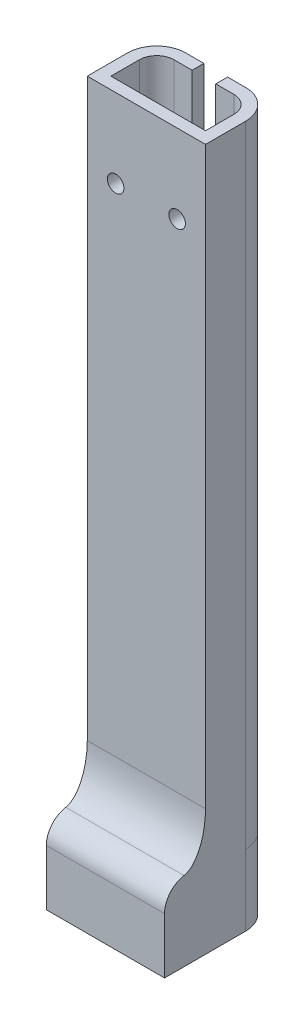
SolidWorks part; units mm, degrees
ref_plane "Front Plane" through (0, 0, 0) normal (0, 0, 1) x (1, 0, 0)
ref_plane "Top Plane" through (0, 0, 0) normal (0, 1, 0) x (1, 0, 0)
ref_plane "Right Plane" through (0, 0, 0) normal (1, 0, 0) x (0, 0, -1)
sketch "Sketch1" plane through (0, 0, 0) normal (0, 1, 0) x (1, 0, 0)
  line L1 (-7.5, 4.4) -> (7.5, 4.4)
  line L2 (-7.5, 4.4) -> (-7.5, -4.4)
  line L3 (-7.5, -4.4) -> (7.5, -4.4)
  line L4 (7.5, 4.4) -> (7.5, -4.4)
  line L5 (-7.5, 4.4) -> (7.5, -4.4) construction
  line L6 (-7.5, -4.4) -> (7.5, 4.4) construction
  point P0 (0, 0)
  dimension "D1" = 15
  dimension "D2" = 8.8
extrude "Boss-Extrude1" add sketch "Sketch1" along normal blind 80
fillet "Fillet1" radius 3.7 2 edges at (7.5, 40, -4.4) (-7.5, 40, -4.4)
sketch "Sketch3" plane through (0, 80, 0) normal (0, 1, 0) x (1, 0, 0)
  line L8 (-6, 0.7) -> (-6, -2.9)
  line L9 (-6, -2.9) -> (6, -2.9)
  line L10 (6, -2.9) -> (6, 0.7)
  line L11 (3.8, 2.9) -> (-3.8, 2.9)
  line L12 (-6, 0.7) -> (-6, -2.9)
  line L13 (-6, -2.9) -> (6, -2.9)
  line L14 (6, -2.9) -> (6, 0.7)
  line L15 (3.8, 2.9) -> (-3.8, 2.9)
  arc A4 (6, 0.7) -> (3.8, 2.9) centre (3.8, 0.7) ccw
  arc A5 (-3.8, 2.9) -> (-6, 0.7) centre (-3.8, 0.7) ccw
  arc A6 (6, 0.7) -> (3.8, 2.9) centre (3.8, 0.7) ccw
  arc A7 (-3.8, 2.9) -> (-6, 0.7) centre (-3.8, 0.7) ccw
  dimension "D1" = 1.5
extrude "Cut-Extrude1" cut sketch "Sketch3" against normal blind 26
sketch "Sketch4" plane through (0, 0, 4.4) normal (0, 0, 1) x (1, 0, 0)
  line L0 (-7.5, 80) -> (7.5, 80) construction
  line L1 (-7.5, 80) -> (-7.5, 0) construction
  line L2 (7.5, 80) -> (7.5, 0) construction
  circle A0 centre (-3.9, 70) radius 1.05
  circle A1 centre (3.9, 70) radius 1.05
  dimension "D3" = 2.1
  dimension "D4" = 2.1
  dimension "D1" = 10
  dimension "D2" = 10
  dimension "D5" = 3.6
  dimension "D6" = 3.6
extrude "Cut-Extrude2" cut sketch "Sketch4" against normal up to surface (1.5 mm away) up to face at (0, 67, 2.9)
sketch "Sketch5" plane through (0, 54, 0) normal (0, 1, 0) x (1, 0, 0)
  line L0 (3.8, 2.9) -> (-3.8, 2.9) construction
  line L1 (-3, 1.7) -> (3, 1.7)
  line L2 (-3, 1.7) -> (-3, -1.3)
  line L3 (-3, -1.3) -> (3, -1.3)
  line L4 (3, 1.7) -> (3, -1.3)
  line L5 (-3, 1.7) -> (3, -1.3) construction
  line L6 (-3, -1.3) -> (3, 1.7) construction
  line L7 (-6, 0.7) -> (-6, -2.9) construction
  point P0 (0, 0.2)
  dimension "D1" = 6
  dimension "D2" = 3
  dimension "D3" = 1.2
  dimension "D4" = 6
extrude "Cut-Extrude3" cut sketch "Sketch5" against normal up to surface (54 mm away) up to face at (0, 0, -0.4888)
fillet "Fillet2" radius 1 4 edges at (3, 27, 1.3) (-3, 27, 1.3) (3, 27, -1.7) (-3, 27, -1.7)
sketch "Sketch6" plane through (0, 0, 0) normal (0, -1, 0) x (1, 0, 0)
  line L1 (-7.5, -4.4) -> (7.5, -4.4)
  line L4 (-7.5, -4.4) -> (-7.5, 9.6)
  line L5 (-7.5, 9.6) -> (7.5, 9.6)
  line L6 (7.5, -4.4) -> (7.5, 9.6)
  dimension "D1" = 14
extrude "Boss-Extrude2" add sketch "Sketch6" along normal blind 9
fillet "Fillet3" radius 3.7 2 edges at (7.5, -4.5, -4.4) (-7.5, -4.5, -4.4)
sketch "Sketch7" plane through (0, -9, 0) normal (0, -1, 0) x (1, 0, 0)
  line L8 (-3.8, -2.6) -> (3.8, -2.6)
  line L9 (5.7, -0.7) -> (5.7, 7.8)
  line L10 (-5.7, 7.8) -> (-5.7, -0.7)
  line L11 (5.7, 7.8) -> (-5.7, 7.8)
  line L12 (-3.8, -2.6) -> (3.8, -2.6)
  line L13 (5.7, -0.7) -> (5.7, 7.8)
  line L14 (-5.7, 7.8) -> (-5.7, -0.7)
  line L15 (5.7, 7.8) -> (-5.7, 7.8)
  arc A4 (-5.7, -0.7) -> (-3.8, -2.6) centre (-3.8, -0.7) ccw
  arc A5 (3.8, -2.6) -> (5.7, -0.7) centre (3.8, -0.7) ccw
  arc A6 (-5.7, -0.7) -> (-3.8, -2.6) centre (-3.8, -0.7) ccw
  arc A7 (3.8, -2.6) -> (5.7, -0.7) centre (3.8, -0.7) ccw
  dimension "D1" = 1.8
extrude "Cut-Extrude4" cut sketch "Sketch7" against normal blind 9
sketch "Sketch9" plane through (0, 80, 0) normal (0, 1, 0) x (1, 0, 0)
  line L0 (3.8, 4.4) -> (-3.8, 4.4) construction
  line L1 (-1.5, 4.4) -> (1.5, 4.4)
  line L5 (-1.5, 4.4) -> (-1.5, 1.4)
  line L6 (-1.5, 1.4) -> (1.5, 1.4)
  line L7 (1.5, 1.4) -> (1.5, 4.4)
  point P6 (0, 4.4)
  dimension "D1" = 3
  dimension "D2" = 3
extrude "Cut-Extrude6" cut sketch "Sketch9" against normal through all
sketch "Sketch10" plane through (0, 0, 0) normal (0, 1, 0) x (1, 0, 0)
  line L1 (-7.5, -4.4) -> (7.5, -4.4)
  line L2 (-7.5, -4.4) -> (-7.5, -9.6)
  line L3 (-7.5, -9.6) -> (7.5, -9.6)
  line L4 (7.5, -4.4) -> (7.5, -9.6)
extrude "Boss-Extrude3" add sketch "Sketch10" along normal blind 1
fillet "Fillet8" radius 6 1 edges at (0, 1, 4.4) second distance 3 first distance on face at (4.95, 70, 4.4)
fillet "Fillet9" radius 3 1 edges at (0, 1, 9.6)
sketch "Sketch11" plane through (0, 0, -4.4) normal (0, 0, -1) x (-1, 0, 0)
  line L0 (3.8, 0) -> (3.8, 80) construction
  line L1 (3.8, 45) -> (7.5, 45)
  line L2 (3.8, 45) -> (3.8, 33)
  line L3 (3.8, 33) -> (7.5, 33)
  line L4 (7.5, 45) -> (7.5, 33)
  line L5 (7.5, 80) -> (7.5, 0) construction
  line L6 (7.5, 80) -> (3.8, 80) construction
  dimension "D1" = 12
  dimension "D2" = 35
extrude "Boss-Extrude5" add sketch "Sketch11" against normal up to vertex (3.7 mm away) up to point (-7.5, 80, -0.7)
sketch "Sketch12" plane through (0, 0, -4.4) normal (0, 0, -1) x (-1, 0, 0)
  line L0 (7.5, 33) -> (7.5, 45) construction
  line L1 (7.5, 42.2) -> (3.3, 42.2)
  line L2 (7.5, 42.2) -> (7.5, 35.8)
  line L3 (7.5, 35.8) -> (3.3, 35.8)
  line L4 (3.3, 42.2) -> (3.3, 35.8)
  line L5 (7.5, 45) -> (3.8, 45) construction
  dimension "D1" = 6.4
  dimension "D2" = 4.2
  dimension "D3" = 2.8
extrude "Cut-Extrude7" cut sketch "Sketch12" against normal blind 6.4
sketch "Sketch13" plane through (0, 0, -4.4) normal (0, 0, -1) x (-1, 0, 0)
  line L0 (1.5, -9) -> (1.5, 80) construction
  line L1 (1.5, 44.2) -> (5.5, 44.2)
  line L3 (1.5, 41.2) -> (5.5, 41.2)
  line L4 (5.5, 44.2) -> (5.5, 41.2)
  line L5 (7.5, 42.2) -> (3.3, 42.2) construction
  line L7 (1.5, 44.2) -> (-1.5, 44.2)
  line L9 (1.5, 41.2) -> (-1.5, 41.2)
  line L10 (-1.5, 44.2) -> (-1.5, 41.2)
  dimension "D1" = 3
  dimension "D2" = 1
  dimension "D3" = 4
extrude "Cut-Extrude8" cut sketch "Sketch13" against normal up to surface (6.4 mm away) up to face at (-5.4, 39, 2)
